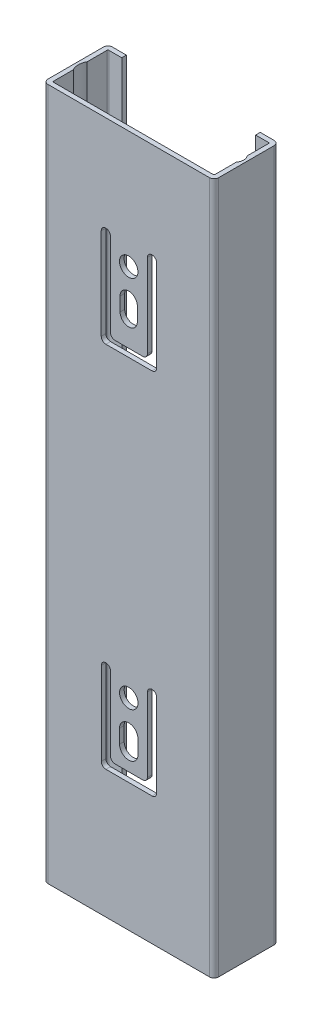
SolidWorks part; units mm, degrees
ref_plane "Front Plane" through (0, 0, 0) normal (0, 0, 1) x (1, 0, 0)
ref_plane "Top Plane" through (0, 0, 0) normal (0, 1, 0) x (1, 0, 0)
ref_plane "Right Plane" through (0, 0, 0) normal (1, 0, 0) x (0, 0, -1)
sketch "Sketch1" plane through (0, 0, 0) normal (0, 1, 0) x (1, 0, 0)
  line L0 (-2.736, -15.432) -> (32.264, -15.432)
  line L1 (32.264, -15.432) -> (32.264, -3.432)
  line L2 (-2.736, -15.432) -> (-2.736, -3.432)
  line L3 (33.264, -2.432) -> (33.264, -16.432)
  line L4 (33.264, -16.432) -> (-3.736, -16.432)
  line L5 (-3.736, -16.432) -> (-3.736, -2.432)
  line L6 (32.264, -3.432) -> (29.264, -3.432)
  line L7 (29.264, -3.432) -> (29.264, -2.432)
  line L8 (29.264, -2.432) -> (33.264, -2.432)
  line L9 (-2.736, -3.432) -> (0.264, -3.432)
  line L10 (0.264, -3.432) -> (0.264, -2.432)
  line L11 (0.264, -2.432) -> (-3.736, -2.432)
  dimension "D1" = 12
  dimension "D2" = 35
  dimension "D3" = 14
  dimension "D4" = 37
  dimension "D5" = 12
  dimension "D6" = 14
  dimension "D7" = 1
  dimension "D8" = 1
  dimension "D9" = 3
  dimension "D10" = 3
extrude "Boss-Extrude1" add sketch "Sketch1" along normal blind 150
fillet "Fillet1" radius 1 4 edges at (-3.736, 75, 2.432) (33.264, 75, 2.432) (33.264, 75, 16.432) (-3.736, 75, 16.432)
fillet "Fillet2" radius 0.2 4 edges at (-2.736, 75, 3.432) (32.264, 75, 3.432) (32.264, 75, 15.432) (-2.736, 75, 15.432)
sketch "Sketch2" plane through (0, 0, 16.432) normal (0, 0, 1) x (1, 0, 0)
  line L2 (-2.736, 0) -> (32.264, 0) construction
  line L3 (14.764, 150) -> (14.764, 0) construction
  circle A0 centre (14.764, 124.5532) radius 2
  point P3 (14.764, 150)
  dimension "D1" = 4
extrude "Cut-Extrude1" cut sketch "Sketch2" against normal through all
sketch "Sketch4" plane through (0, 0, 16.432) normal (0, 0, 1) x (1, 0, 0)
  line L0 (14.764, 150) -> (14.764, 0) construction
  line L1 (-2.736, 150) -> (32.264, 150) construction
  line L2 (-2.736, 0) -> (32.264, 0) construction
  line L3 (14.764, 118.1003) -> (14.764, 115.1003) construction
  line L4 (16.6324, 118.1003) -> (16.6324, 115.1003)
  line L5 (12.8955, 118.1003) -> (12.8955, 115.1003)
  arc A0 (16.6324, 118.1003) -> (12.8955, 118.1003) centre (14.764, 118.1003) ccw
  arc A1 (12.8955, 115.1003) -> (16.6324, 115.1003) centre (14.764, 115.1003) ccw
  point P8 (14.764, 116.6003)
  dimension "D1" = 3
extrude "Cut-Extrude2" cut sketch "Sketch4" against normal through all
sketch "Sketch6" plane through (0, 0, 16.432) normal (0, 0, 1) x (1, 0, 0)
  line L0 (18.8102, 129.2928) -> (18.8102, 109.229)
  line L1 (18.8102, 109.229) -> (10.8102, 109.229)
  line L2 (10.8102, 109.229) -> (10.8102, 129.2928)
  line L3 (10.8102, 129.2928) -> (8.8102, 129.2928)
  line L4 (8.8102, 129.2928) -> (8.8102, 107.5092)
  line L5 (8.8102, 107.5092) -> (20.8102, 107.5092)
  line L6 (20.8102, 107.5092) -> (20.8102, 129.2928)
  line L7 (20.8102, 129.2928) -> (18.8102, 129.2928)
  line L8 (-2.736, 150) -> (32.264, 150) construction
  line L9 (14.764, 150) -> (14.764, 103.5331) construction
  dimension "D1" = 8
  dimension "D2" = 2
  dimension "D3" = 12
  dimension "D4" = 21.7836
extrude "Cut-Extrude3" cut sketch "Sketch6" against normal blind 150
fillet "Fillet7" radius 1 8 edges at (8.8102, 107.5092, 15.932) (20.8102, 107.5092, 15.932) (18.8102, 109.229, 15.932) (10.8102, 109.229, 15.932) (10.8102, 129.2928, 15.932) (8.8102, 129.2928, 15.932) (18.8102, 129.2928, 15.932) (20.8102, 129.2928, 15.932)
sketch "Sketch7" plane through (0, 0, 16.432) normal (0, 0, 1) x (1, 0, 0)
  line L0 (14.764, 0) -> (14.8102, 107.5092) construction
  line L1 (-2.736, 0) -> (32.264, 0) construction
  line L2 (9.8102, 107.5092) -> (19.8102, 107.5092) construction
  line L3 (14.7799, 36.9339) -> (14.7786, 33.9339) construction
  line L4 (16.7799, 36.9331) -> (16.7786, 33.9331)
  line L5 (12.7799, 36.9348) -> (12.7786, 33.9348)
  circle A0 centre (14.7827, 43.6164) radius 2
  arc A1 (16.7799, 36.9331) -> (12.7799, 36.9348) centre (14.7799, 36.9339) ccw
  arc A2 (12.7786, 33.9348) -> (16.7786, 33.9331) centre (14.7786, 33.9339) ccw
  point P10 (14.7792, 35.4339)
  dimension "D1" = 4
  dimension "D2" = 3
extrude "Cut-Extrude4" cut sketch "Sketch7" against normal through all
sketch "Sketch8" plane through (0, 0, 16.432) normal (0, 0, 1) x (1, 0, 0)
  line L0 (18.7589, 48.4854) -> (18.7589, 28.4854)
  line L1 (18.7589, 28.4854) -> (10.7589, 28.4854)
  line L2 (10.7589, 28.4854) -> (10.7589, 48.5267)
  line L3 (8.7589, 48.4854) -> (10.7589, 48.5267)
  line L4 (20.7589, 48.4854) -> (20.7589, 26.4854)
  line L5 (20.7589, 26.4854) -> (8.7589, 26.4854)
  line L6 (8.7589, 26.4854) -> (8.7589, 48.4854)
  line L7 (18.7589, 48.4854) -> (20.7589, 48.4854)
  line L8 (14.764, 0) -> (14.7827, 45.6164)
  line L9 (-2.736, 0) -> (32.264, 0) construction
  circle A0 centre (14.7827, 43.6164) radius 2 construction
  dimension "D1" = 20
  dimension "D2" = 22
  dimension "D3" = 2
  dimension "D4" = 2
  dimension "D5" = 2
  dimension "D6" = 22
  dimension "D7" = 8
sketch "Sketch9" plane through (0, 0, 16.432) normal (0, 0, 1) x (1, 0, 0)
  line L0 (18.8244, 47.7393) -> (18.8244, 29.7393)
  line L1 (18.8244, 29.7393) -> (10.8244, 29.7393)
  line L2 (10.8244, 29.7393) -> (10.8244, 47.7393)
  line L3 (10.8244, 47.7393) -> (8.8244, 47.7393)
  line L4 (8.8244, 47.7393) -> (8.8244, 27.7393)
  line L5 (8.8244, 27.7393) -> (20.8244, 27.7393)
  line L6 (20.8244, 27.7393) -> (20.8244, 47.7393)
  line L7 (18.8244, 47.7393) -> (20.8244, 47.7393)
  dimension "D1" = 2
  dimension "D2" = 8
  dimension "D3" = 12
  dimension "D4" = 20
  dimension "D5" = 18
  dimension "D6" = 20
  dimension "D7" = 18
extrude "Cut-Extrude6" cut sketch "Sketch9" against normal through all
fillet "Fillet9" radius 1 8 edges at (20.8244, 27.7393, 15.932) (18.8244, 29.7393, 15.932) (8.8244, 27.7393, 15.932) (10.8244, 29.7393, 15.932) (8.8244, 47.7393, 15.932) (10.8244, 47.7393, 15.932) (18.8244, 47.7393, 15.932) (20.8244, 47.7393, 15.932)
ref_plane "Plane5" through (32.264, 150, 3.632) normal (0, 0, 1) x (1, 0, 0)
sketch "Sketch12" plane through (0, 150, 0) normal (0, 1, 0) x (1, 0, 0)
  line L0 (33.264, -9.432) -> (30.666, -9.432) construction
  line L1 (33.264, -15.432) -> (33.264, -3.432) construction
  line L4 (-3.736, -3.432) -> (-3.736, -15.432) construction
  line L5 (-3.736, -9.432) -> (-0.138, -9.432) construction
  circle A0 centre (30.666, -9.432) radius 2
  circle A1 centre (-0.138, -9.432) radius 3
  dimension "D1" = 2.598
  dimension "D3" = 3.598
extrude "Cut-Extrude7" cut sketch "Sketch12" against normal through all
